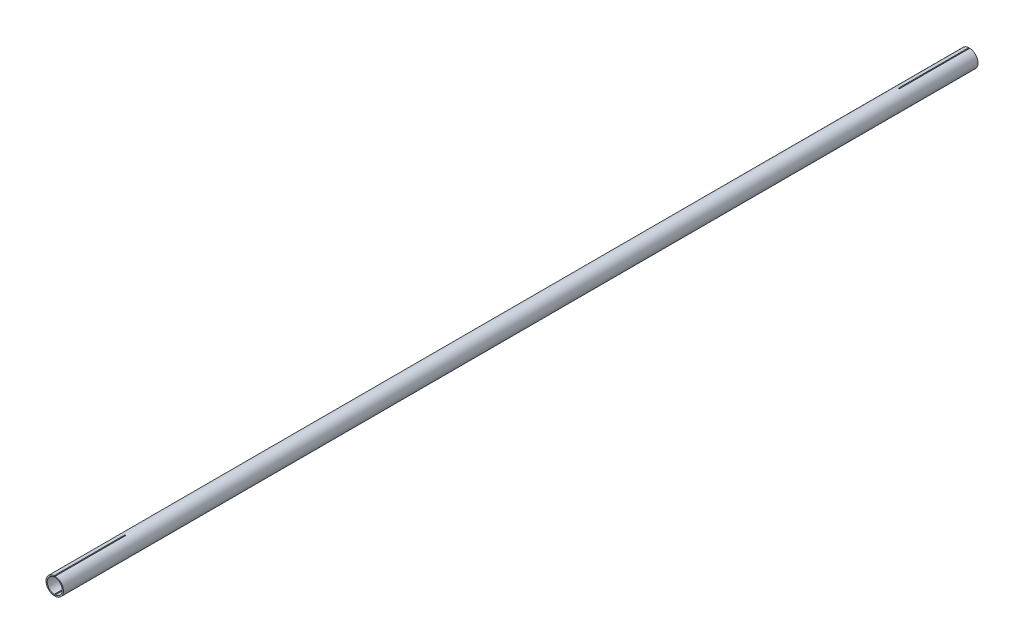
SolidWorks part; units mm, degrees
ref_plane "Front Plane" through (0, 0, 0) normal (0, 0, 1) x (1, 0, 0)
ref_plane "Top Plane" through (0, 0, 0) normal (0, 1, 0) x (1, 0, 0)
ref_plane "Right Plane" through (0, 0, 0) normal (1, 0, 0) x (0, 0, -1)
sketch "Sketch1" plane through (0, 0, 0) normal (0, 0, 1) x (1, 0, 0)
  circle A0 centre (0, 0) radius 17.46
  circle A1 centre (0, 0) radius 15
  dimension "D1" = 34.92
  dimension "D2" = 30
extrude "Boss-Extrude1" add sketch "Sketch1" along normal blind 1828.8
sketch "Sketch2" plane through (0, 0, 0) normal (0, 1, 0) x (1, 0, 0)
  line L0 (0, 0) -> (0, -15) construction
  line L1 (0, -19) -> (0, -31) construction
  circle A0 centre (0, -15) radius 4
  circle A1 centre (0, -31) radius 4
  dimension "D2" = 8
  dimension "D4" = 8
  dimension "D1" = 15
  dimension "D3" = 12
sketch "Sketch4" plane through (0, 0, 0) normal (0, 0, 1) x (1, 0, 0)
  line L0 (0, 17.46) -> (0, -17.46) construction
  line L1 (2.54, 15) -> (-2.54, 15) construction
  line L2 (0, 0) -> (5.9684, 0) construction
  line L3 (2.54, -15) -> (-2.54, -15) construction
  line L5 (1.04, -25) -> (-1.04, -25)
  line L6 (1.04, -25) -> (1.04, 25)
  line L7 (1.04, 25) -> (-1.04, 25)
  line L8 (-1.04, -25) -> (-1.04, 25)
  line L9 (1.04, -25) -> (-1.04, 25) construction
  line L10 (1.04, 25) -> (-1.04, -25) construction
  circle A0 centre (0, 0) radius 17.46 construction
  circle A1 centre (0, 0) radius 15 construction
  point P10 (0, 15)
  dimension "D1" = 2.54
  dimension "D2" = 50
  dimension "D3" = 2.08
extrude "Cut-Extrude2" cut sketch "Sketch4" along normal blind 141
sketch "Sketch7" plane through (0, 0, 1828.8) normal (0, 0, 1) x (1, 0, 0)
  line L1 (-1.04, 25) -> (1.04, 25)
  line L2 (-1.04, 25) -> (-1.04, -25)
  line L3 (-1.04, -25) -> (1.04, -25)
  line L4 (1.04, 25) -> (1.04, -25)
  line L5 (-1.04, 25) -> (1.04, -25) construction
  line L6 (-1.04, -25) -> (1.04, 25) construction
  point P0 (0, 0)
  dimension "D1" = 2.08
  dimension "D2" = 50
extrude "Cut-Extrude3" cut sketch "Sketch7" against normal blind 141
sketch "Sketch8" plane through (0, 0, 0) normal (0, 1, 0) x (1, 0, 0)
  line L0 (0, 69.836) -> (0, -15) construction
ref_axis "Axis1" through (0, 0, -69.836) along (0, 0, 1)
